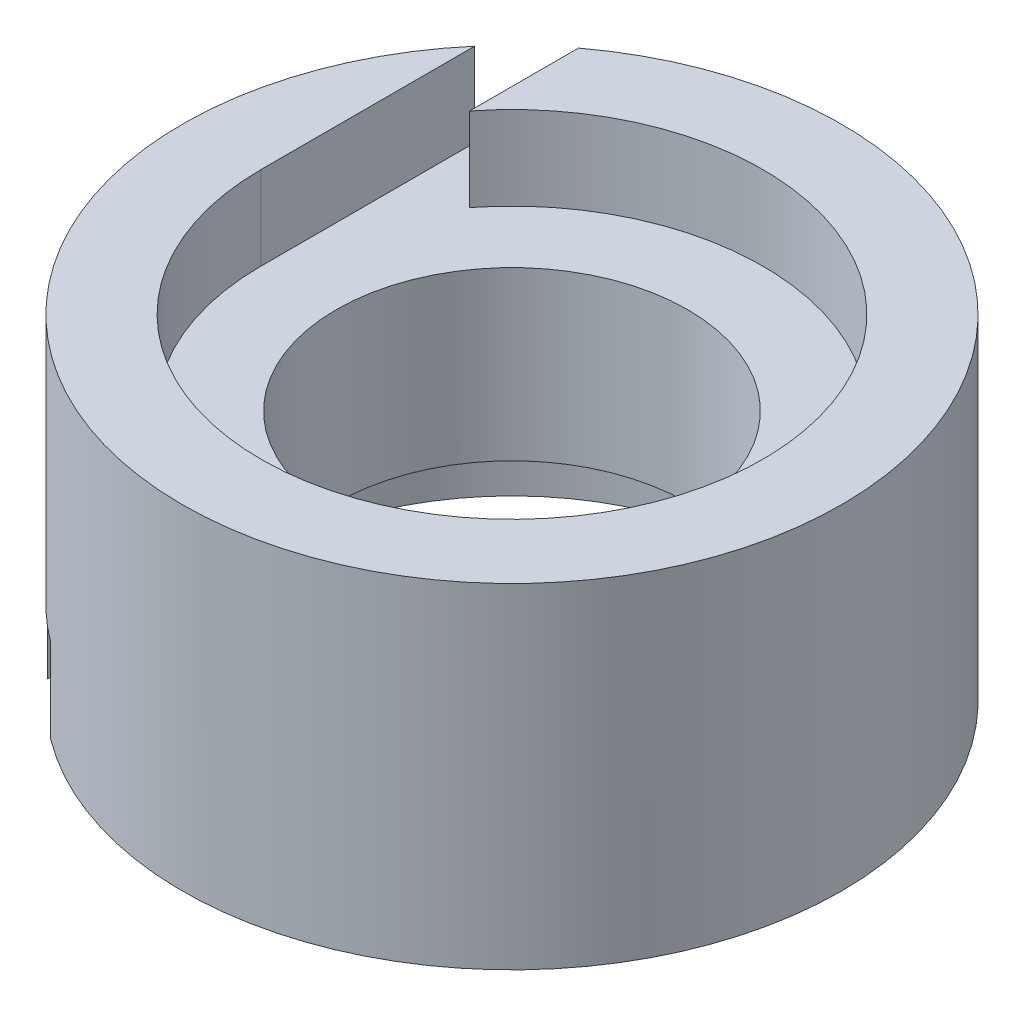
SolidWorks part; units mm, degrees
ref_plane "Front Plane" through (0, 0, 0) normal (0, 0, 1) x (1, 0, 0)
ref_plane "Top Plane" through (0, 0, 0) normal (0, 1, 0) x (1, 0, 0)
ref_plane "Right Plane" through (0, 0, 0) normal (1, 0, 0) x (0, 0, -1)
sketch "Sketch1" plane through (0, 0, 0) normal (0, 1, 0) x (1, 0, 0)
  circle A0 centre (0, 0) radius 25.019
  circle A1 centre (0, 0) radius 13.335
  dimension "D1" = 50.038
  dimension "D2" = 26.67
extrude "Boss-Extrude1" add sketch "Sketch1" along normal mid plane 25.4
sketch "Sketch2" plane through (0, 12.7, 0) normal (0, 1, 0) x (1, 0, 0)
  line L0 (-19.05, 0) -> (-19.05, 16.2188)
  line L1 (-14.986, 11.7611) -> (-14.986, 20.0342)
  arc A0 (-19.05, 0) -> (-14.986, 11.7611) centre (0, 0) ccw
  circle A1 centre (0, 0) radius 25.019 construction
  arc A2 (-14.986, 20.0342) -> (-19.05, 16.2188) centre (0, 0) ccw
  dimension "D1" = 4.064
  dimension "D2" = 19.05
extrude "Cut-Extrude1" cut sketch "Sketch2" against normal blind 6.35
ref_axis "Axis1" through (34.925, 0, 0) along (-1, 0, 0)
sketch "Sketch9" plane through (0, 0, 0) normal (0, 0, 1) x (1, 0, 0)
  line L0 (0, -22.352) -> (0, 22.352) construction
  line L1 (-20.066, 3.81) -> (-14.478, 3.81)
  line L2 (-20.066, 3.81) -> (-20.066, 0)
  line L3 (-20.066, 0) -> (-14.478, 0)
  line L4 (-14.478, 3.81) -> (-14.478, 0)
  point P5 (-14.478, 1.905)
  dimension "D1" = 3.81
  dimension "D2" = 14.478
sketch "Sketch12" plane through (0, 6.35, 0) normal (0, 1, 0) x (1, 0, 0)
  circle A0 centre (0, 0) radius 13.335
  circle A1 centre (0, 0) radius 13.335 construction
curve "Helix/Spiral2" pitch 3.302 height 2.9619 turns 0.897
pattern_circular "CirPattern1" count 2 every 180 about axis through (34.925, 0, 0) along (-1, 0, 0) of "Cut-Extrude1"
